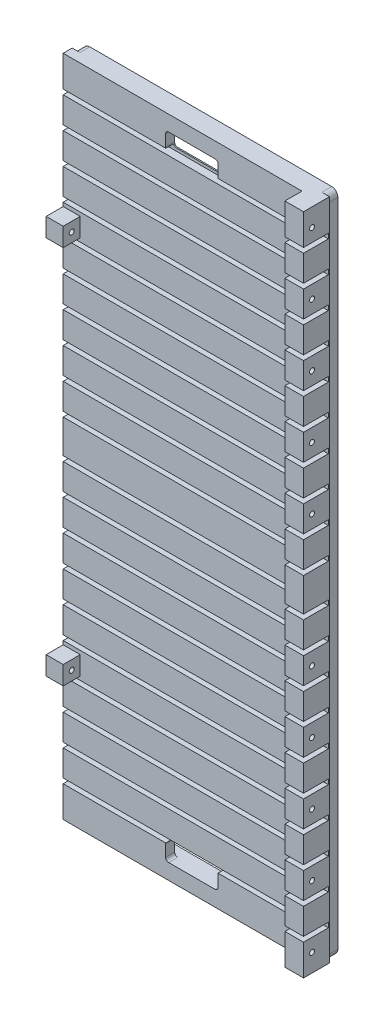
SolidWorks part; units mm, degrees
material "6061-T6 (SS)"
ref_plane "Front Plane" through (0, 0, 0) normal (0, 0, 1) x (1, 0, 0)
ref_plane "Top Plane" through (0, 0, 0) normal (0, 1, 0) x (1, 0, 0)
ref_plane "Right Plane" through (0, 0, 0) normal (1, 0, 0) x (0, 0, -1)
sketch "Sketch1" plane through (0, 0, 0) normal (0, 0, 1) x (1, 0, 0)
  line L1 (-41.5, -107) -> (41.5, -107)
  line L2 (-41.5, -107) -> (-41.5, 107)
  line L3 (-41.5, 107) -> (41.5, 107)
  line L4 (41.5, -107) -> (41.5, 107)
  line L5 (-41.5, -107) -> (41.5, 107) construction
  line L6 (-41.5, 107) -> (41.5, -107) construction
  point P0 (0, 0)
  dimension "D1" = 83
  dimension "D2" = 214
extrude "Boss-Extrude1" add sketch "Sketch1" along normal blind 8.4
sketch "Sketch2" plane through (0, 107, 0) normal (0, 1, 0) x (1, 0, 0)
  line L0 (41.5, -8.4) -> (41.5, 0) construction
  line L1 (-41.5, -8.4) -> (35.5, -8.4)
  line L2 (-41.5, -8.4) -> (-41.5, -2.9)
  line L3 (-41.5, -2.9) -> (35.5, -2.9)
  line L4 (35.5, -8.4) -> (35.5, -2.9)
  dimension "D1" = 5.5
  dimension "D2" = 6
extrude "Cut-Extrude1" cut sketch "Sketch2" against normal through all
sketch "Sketch3" plane through (41.5, 0, 0) normal (1, 0, 0) x (0, 0, -1)
  line L0 (-8.4, -107) -> (-8.4, 107) construction
  line L1 (-8.4, 97) -> (-0.4, 97)
  line L2 (-8.4, 97) -> (-8.4, 95.4)
  line L3 (-8.4, 95.4) -> (-0.4, 95.4)
  line L4 (-0.4, 97) -> (-0.4, 95.4)
  line L5 (-8.4, 107) -> (0, 107) construction
  dimension "D1" = 1.6
  dimension "D2" = 8
  dimension "D3" = 10
extrude "Cut-Extrude2" cut sketch "Sketch3" against normal through all
pattern_linear "LPattern1" count 10 spacing 10 along (0, -1, 0) of "Cut-Extrude2"
mirror "Mirror1" about plane through (0, 0, 0) normal (0, 1, 0) of "LPattern1"
sketch "Sketch4" plane through (0, 0, 0) normal (0, 0, -1) x (-1, 0, 0)
  line L0 (-41.5, 107) -> (41.5, 107) construction
  line L1 (-39, 107) -> (39, 107)
  line L2 (-41, 105) -> (-41, -105)
  line L3 (-39, -107) -> (39, -107)
  line L4 (41, 105) -> (41, -105)
  line L5 (-33.5, -102) -> (33.5, -102)
  line L6 (-35.5, -100) -> (-35.5, 100)
  line L7 (-33.5, 102) -> (33.5, 102)
  line L8 (35.5, -100) -> (35.5, 100)
  line L9 (-35.5, -102) -> (35.5, 102) construction
  line L10 (-35.5, 102) -> (35.5, -102) construction
  line L11 (41.5, -107) -> (-41.5, -107) construction
  arc A0 (-41, -105) -> (-39, -107) centre (-39, -105) ccw
  arc A1 (39, -107) -> (41, -105) centre (39, -105) ccw
  arc A2 (39, 107) -> (41, 105) centre (39, 105) cw
  arc A3 (-39, 107) -> (-41, 105) centre (-39, 105) ccw
  arc A4 (33.5, -102) -> (35.5, -100) centre (33.5, -100) ccw
  arc A5 (-33.5, -102) -> (-35.5, -100) centre (-33.5, -100) cw
  arc A6 (-35.5, 100) -> (-33.5, 102) centre (-33.5, 100) cw
  arc A7 (33.5, 102) -> (35.5, 100) centre (33.5, 100) cw
  point P10 (41.5, -107)
  point P15 (-41.5, 107)
  point P16 (0, 0)
  dimension "D1" = 2
  dimension "D4" = 2
  dimension "D2" = 5
  dimension "D3" = 5.5
  dimension "D5" = 41
  dimension "D6" = 41
extrude "Boss-Extrude2" add sketch "Sketch4" along normal blind 3.18
sketch "Sketch5" plane through (0, 0, 2.9) normal (0, 0, 1) x (1, 0, 0)
  line L0 (-41.5, 57) -> (-41.5, 65.4) construction
  line L1 (-36, 58.2) -> (-41.5, 58.2)
  line L2 (-36, 58.2) -> (-36, 64.2)
  line L3 (-36, 64.2) -> (-41.5, 64.2)
  line L4 (-41.5, 58.2) -> (-41.5, 64.2)
  line L5 (-36, 58.2) -> (-41.5, 64.2) construction
  line L6 (-36, 64.2) -> (-41.5, 58.2) construction
  line L8 (35.5, 65.4) -> (-41.5, 65.4) construction
  point P0 (-38.75, 61.2)
  dimension "D1" = 6
  dimension "D2" = 5.5
  dimension "D3" = 4.2
extrude "Boss-Extrude3" add sketch "Sketch5" along normal blind 5.5
mirror "Mirror2" about plane through (0, 0, 0) normal (0, 1, 0) of "Boss-Extrude3"
sketch "Sketch6" plane through (0, 0, 0) normal (0, 0, -1) x (-1, 0, 0)
  line L0 (33.5, 102) -> (-33.5, 102) construction
  line L1 (-7.475, 96.3) -> (7.475, 96.3)
  line L2 (-8.475, 97.3) -> (-8.475, 101)
  line L3 (-7.475, 102) -> (7.475, 102)
  line L4 (8.475, 97.3) -> (8.475, 101)
  line L5 (-8.475, 96.3) -> (8.475, 102) construction
  line L6 (-8.475, 102) -> (8.475, 96.3) construction
  arc A0 (-8.475, 101) -> (-7.475, 102) centre (-7.475, 101) cw
  arc A1 (7.475, 102) -> (8.475, 101) centre (7.475, 101) cw
  arc A2 (7.475, 96.3) -> (8.475, 97.3) centre (7.475, 97.3) ccw
  arc A3 (-7.475, 96.3) -> (-8.475, 97.3) centre (-7.475, 97.3) cw
  point P0 (0, 99.15)
  dimension "D3" = 1
  dimension "D1" = 5.7
  dimension "D2" = 16.95
extrude "Cut-Extrude3" cut sketch "Sketch6" against normal through all
mirror "Mirror3" about plane through (0, 0, 0) normal (0, 1, 0) of "Cut-Extrude3"
hole_wizard "M2x0.4 Tapped Hole1" positions "Sketch8" profile "Sketch7" tap size "M2x0.4" standard "ANSI Metric" end condition through all
sketch "Sketch8" plane through (41.5, 0, 0) normal (1, 0, 0) x (0, 0, -1)
  line L0 (-8.4, 97) -> (-8.4, 107) construction
  line L1 (-8.4, 107) -> (0, 107) construction
  line L2 (0, 0) -> (-25.7972, 0) construction
  line L3 (0, -107) -> (0, 107) construction
  point P0 (-5.65, 101.2)
  point P16 (-5.65, 81.2)
  point P17 (-5.65, 61.2)
  point P18 (-5.65, 41.2)
  point P19 (-5.65, 21.2)
  point P34 (-5.65, -101.2)
  point P35 (-5.65, -81.2)
  point P36 (-5.65, -61.2)
  point P37 (-5.65, -41.2)
  point P38 (-5.65, -21.2)
  dimension "D1" = 2.75
  dimension "D2" = 5.8
  dimension "D3" = 5
sketch "Sketch7" plane through (41.5, 101.2, 5.65) normal (0, 1, 0) x (0, 0, -1)
  line L0 (0, 0) -> (0, 83)
  line L1 (0, 83) -> (0.8, 83)
  line L2 (0.8, 83) -> (0.8, 0)
  line L5 (0.8, 0) -> (0, 0)
  line L11 (0, -6.35) -> (0, 107.95) construction
  dimension "Thread Major Dia." = 1.6
  dimension "Thru Tap Drill Depth" = 83
hole_wizard "M2x0.4 Tapped Hole2" positions "Sketch10" profile "Sketch11" tap size "M2x0.4" standard "ANSI Metric"
sketch "Sketch10" plane through (0, 0, -3.18) normal (0, 0, -1) x (-1, 0, 0)
  line L0 (39, 107) -> (-39, 107) construction
  line L1 (-41, 105) -> (-41, -105) construction
  line L3 (-35.5, 0) -> (35.5, 0) construction
  line L4 (-35.5, 100) -> (-35.5, -100) construction
  line L5 (35.5, -100) -> (35.5, 100) construction
  point P0 (-37.5, 101.2)
  point P15 (37.5, 101.2)
  point P16 (37.5, 81.2)
  point P17 (37.5, 61.2)
  point P18 (37.5, 41.2)
  point P19 (37.5, 21.2)
  point P20 (-37.5, 81.2)
  point P21 (-37.5, 61.2)
  point P22 (-37.5, 41.2)
  point P23 (-37.5, 21.2)
  point P32 (37.5, -101.2)
  point P33 (-37.5, -21.2)
  point P34 (-37.5, -41.2)
  point P35 (-37.5, -61.2)
  point P36 (-37.5, -81.2)
  point P37 (37.5, -21.2)
  point P38 (37.5, -41.2)
  point P39 (37.5, -61.2)
  point P40 (37.5, -81.2)
  point P41 (-37.5, -101.2)
  dimension "D1" = 5.8
  dimension "D2" = 3.5
  dimension "D5" = 2
  dimension "D3" = 5
sketch "Sketch11" plane through (37.5, 101.2, -3.18) normal (1, 0, 0) x (0, 1, 0)
  line L0 (0, 0) -> (0, 4.4807)
  line L1 (0, 4.4807) -> (0.8, 4)
  line L2 (0.8, 4) -> (0.8, 0)
  line L5 (0.8, 0) -> (0, 0)
  line L10 (0, 4.4807) -> (-0.8, 4) construction
  line L11 (0, -6.35) -> (0, 107.95) construction
  dimension "Tap Drill Dia." = 1.6
  dimension "Tap Drill Depth" = 4
  dimension "Drill Angle" = 118
sketch "Sketch12" plane through (0, 0, 2.9) normal (0, 0, 1) x (1, 0, 0)
  line L1 (28, 71.95) -> (34.5, 71.95)
  line L2 (27, 72.95) -> (27, 79.45)
  line L3 (28, 80.45) -> (34.5, 80.45)
  line L4 (35.5, 72.95) -> (35.5, 79.45)
  line L5 (-35.714, 77) -> (-35.714, 75.4) construction
  line L6 (-41.5, 77) -> (35.5, 77) construction
  line L7 (35.5, 75.4) -> (-41.5, 75.4) construction
  line L8 (41.5, 67) -> (41.5, 75.4) construction
  arc A0 (35.5, 72.95) -> (34.5, 71.95) centre (34.5, 72.95) cw
  arc A1 (34.5, 80.45) -> (35.5, 79.45) centre (34.5, 79.45) cw
  arc A2 (27, 79.45) -> (28, 80.45) centre (28, 79.45) cw
  arc A3 (27, 72.95) -> (28, 71.95) centre (28, 72.95) ccw
  point P6 (27, 76.2)
  point P19 (-35.714, 76.2)
  dimension "D1" = 1
  dimension "D2" = 8.5
  dimension "D3" = 8.5
  dimension "D4" = 6
extrude "wonky_+Y_RBF_hole" [suppressed] cut sketch "Sketch12" against normal blind 10
